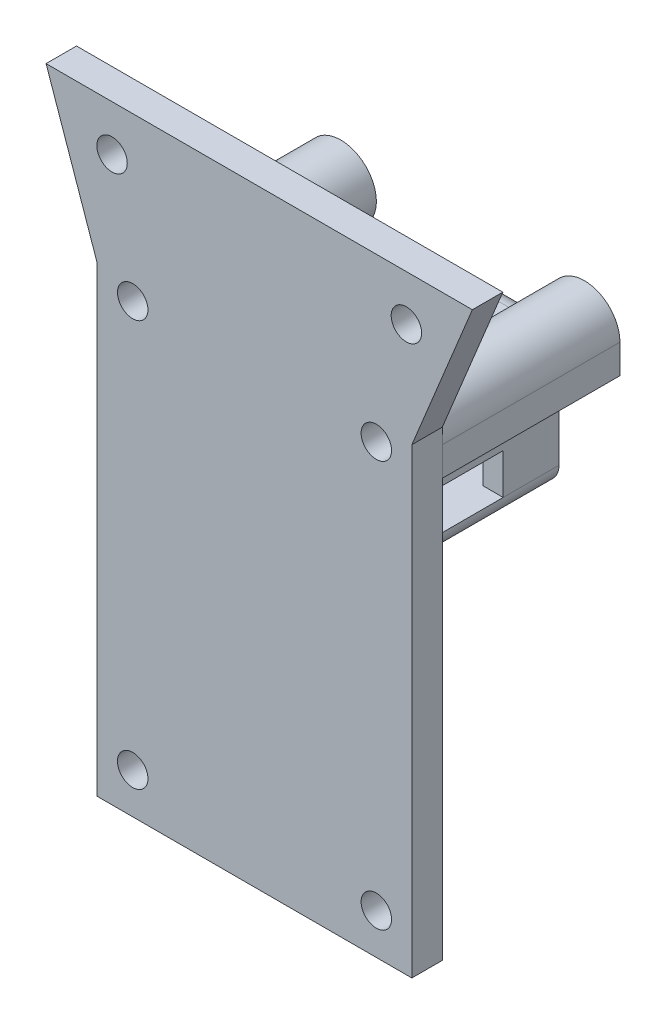
SolidWorks part; units mm, degrees
other "Markup1"
sketch "Sketch10" plane through (36.963, 0, 3) normal (0.1421, -0.5407, 0.8291) x (-0.9838, -0.1695, 0.058)
sketch "Sketch14" plane through (36.963, 0, 3) normal (0.1421, -0.5407, 0.8291) x (-0.9838, -0.1695, 0.058)
ref_plane "Front Plane" through (0, 0, 0) normal (0, 0, 1) x (1, 0, 0)
ref_plane "Top Plane" through (0, 0, 0) normal (0, 1, 0) x (1, 0, 0)
ref_plane "Right Plane" through (0, 0, 0) normal (1, 0, 0) x (0, 0, -1)
sketch "Sketch1" plane through (0, 0, 0) normal (0, 0, 1) x (1, 0, 0)
  line L1 (0, 0) -> (31, 0)
  line L2 (0, 0) -> (0, 45.5)
  line L3 (-5.037, 60) -> (36.963, 60)
  line L4 (31, 0) -> (31, 45.5)
  line L5 (36.963, 60) -> (31, 45.5)
  line L7 (-5.037, 60) -> (0, 45.5)
  circle A0 centre (30.463, 55.5) radius 1.5
  circle A1 centre (27.5, 44) radius 1.5
  circle A4 centre (27.5, 4) radius 1.5
  circle A5 centre (3.5, 4) radius 1.5
  circle A7 centre (3.5, 44) radius 1.5
  circle A9 centre (1.463, 55.5) radius 1.5
  point P29 (15.963, 60)
  dimension "D4" = 3
  dimension "D5" = 21
  dimension "D6" = 2
  dimension "D7" = 2
  dimension "D8" = 21
  dimension "D9" = 2.5
  dimension "D10" = 37
  dimension "D11" = 2.8
  dimension "D12" = 29
  dimension "D13" = 14.5
  dimension "D14" = 11.5
  dimension "D15" = 3
  dimension "D16" = 5
  dimension "D2" = 0
  dimension "D3" = 31
extrude "Boss-Extrude1" add sketch "Sketch1" along normal blind 3
sketch "Sketch2" plane through (0, 0, 0) normal (0, 0, -1) x (-1, 0, 0)
  line L1 (0, 44) -> (0, 24.5)
  line L3 (0, 45.5) -> (0, 0) construction
  line L4 (0, 24.5) -> (-18, 24.5)
  line L8 (-31, 44) -> (-31, 41.136)
  line L9 (-31, 0) -> (-31, 45.5) construction
  line L11 (-18, 24.5) -> (-18, 28.5)
  line L12 (-18, 28.5) -> (-25, 28.5)
  line L14 (-24.0359, 43.5) -> (-6.9641, 43.5)
  line L16 (-25, 28.5) -> (-25, 35.136)
  line L17 (-25, 35.136) -> (-31, 41.136)
  circle A0 centre (-3.5, 44) radius 1.5 construction
  circle A1 centre (-27.5, 44) radius 1.5 construction
  circle A2 centre (-3.5, 44) radius 1.5 construction
  circle A3 centre (-27.5, 44) radius 1.5 construction
  circle A4 centre (-27.5, 44) radius 2.5
  circle A5 centre (-3.5, 44) radius 2.5
  arc A6 (0, 44) -> (-6.9641, 43.5) centre (-3.5, 44) ccw
  arc A7 (-24.0359, 43.5) -> (-31, 44) centre (-27.5, 44) ccw
  dimension "D1" = 5
  dimension "D2" = 7
  dimension "D3" = 5
  dimension "D4" = 7
  dimension "D6" = 18
  dimension "D9" = 2
  dimension "D10" = 45
  dimension "D11" = 2
  dimension "D8" = 15
  dimension "D5" = 19
  dimension "D7" = 25
extrude "Boss-Extrude2" add sketch "Sketch2" along normal blind 1.5 separate body
sketch "Sketch5" plane through (0, 0, -1.5) normal (0, 0, -1) x (-1, 0, 0)
  line L0 (-23, 41.5) -> (-5.5, 41.5)
  line L1 (-5.5, 42.5) -> (-5.5, 41.5)
  line L2 (-6.9641, 43.5) -> (-24.0359, 43.5) construction
  line L3 (-2, 42) -> (-2, 26.5)
  line L4 (-2, 26.5) -> (-16, 26.5)
  line L5 (-16, 26.5) -> (-16, 30.5)
  line L6 (-16, 30.5) -> (-23, 30.5)
  line L7 (-23, 30.5) -> (-23, 41.5)
  line L11 (-6.9641, 43.5) -> (-24.0359, 43.5)
  line L12 (-31, 44) -> (-31, 41.136)
  line L13 (-31, 41.136) -> (-25, 35.136)
  line L14 (-25, 35.136) -> (-25, 28.5)
  line L15 (-25, 28.5) -> (-18, 28.5)
  line L16 (-18, 28.5) -> (-18, 24.5)
  line L17 (-18, 24.5) -> (0, 24.5)
  line L18 (0, 24.5) -> (0, 44)
  line L19 (-6.9641, 43.5) -> (-24.0359, 43.5)
  line L20 (-31, 44) -> (-31, 41.136)
  line L21 (-31, 41.136) -> (-25, 35.136)
  line L22 (-25, 35.136) -> (-25, 28.5)
  line L23 (-25, 28.5) -> (-18, 28.5)
  line L24 (-18, 28.5) -> (-18, 24.5)
  line L25 (-18, 24.5) -> (0, 24.5)
  line L26 (0, 24.5) -> (0, 44)
  circle A0 centre (-3.5, 44) radius 2.5 construction
  circle A1 centre (-27.5, 44) radius 2.5 construction
  arc A2 (-2, 42) -> (-5.5, 42.5) centre (-3.5, 44) ccw
  arc A3 (0, 44) -> (-6.9641, 43.5) centre (-3.5, 44) ccw
  arc A4 (-24.0359, 43.5) -> (-31, 44) centre (-27.5, 44) ccw
  arc A5 (0, 44) -> (-6.9641, 43.5) centre (-3.5, 44) ccw
  arc A6 (-24.0359, 43.5) -> (-31, 44) centre (-27.5, 44) ccw
  circle A7 centre (-27.5, 44) radius 2.5
  dimension "D1" = 2
  dimension "D3" = 2
  dimension "D4" = 2
  dimension "D5" = 2
  dimension "D6" = 2
  dimension "D7" = 2
  dimension "D8" = 2
  dimension "D2" = 0
extrude "Boss-Extrude5" add sketch "Sketch5" along normal blind 14
sketch "Sketch6" plane through (0, 0, -15.5) normal (0, 0, -1) x (-1, 0, 0)
  line L8 (-6.9641, 43.5) -> (-24.0359, 43.5)
  line L9 (-31, 44) -> (-31, 41.136)
  line L10 (-31, 41.136) -> (-25, 35.136)
  line L11 (-25, 35.136) -> (-25, 28.5)
  line L12 (-25, 28.5) -> (-18, 28.5)
  line L13 (-18, 28.5) -> (-18, 24.5)
  line L14 (-18, 24.5) -> (0, 24.5)
  line L15 (0, 24.5) -> (0, 44)
  line L16 (-6.9641, 43.5) -> (-24.0359, 43.5)
  line L17 (-31, 44) -> (-31, 41.136)
  line L18 (-31, 41.136) -> (-25, 35.136)
  line L19 (-25, 35.136) -> (-25, 28.5)
  line L20 (-25, 28.5) -> (-18, 28.5)
  line L21 (-18, 28.5) -> (-18, 24.5)
  line L22 (-18, 24.5) -> (0, 24.5)
  line L23 (0, 24.5) -> (0, 44)
  arc A1 (-2, 42) -> (-5.5, 42.5) centre (-3.5, 44) ccw construction
  arc A2 (0, 44) -> (-6.9641, 43.5) centre (-3.5, 44) ccw
  arc A3 (-24.0359, 43.5) -> (-31, 44) centre (-27.5, 44) ccw
  arc A4 (0, 44) -> (-6.9641, 43.5) centre (-3.5, 44) ccw
  arc A5 (-24.0359, 43.5) -> (-31, 44) centre (-27.5, 44) ccw
  circle A6 centre (-27.5, 44) radius 2.5 construction
  circle A8 centre (-3.5, 44) radius 2.5
  circle A9 centre (-27.5, 44) radius 2.5
  dimension "D1" = 0
extrude "Boss-Extrude6" add sketch "Sketch6" along normal blind 2
sketch "Sketch8" plane through (0, 0, 0) normal (-1, 0, 0) x (0, 0, 1)
  line L0 (-4, 24.5) -> (-4, 33.5)
  line L1 (-17.5, 24.5) -> (0, 24.5) construction
  line L2 (-4, 33.5) -> (-13.5, 33.5)
  line L3 (-13.5, 33.5) -> (-13.5, 24.5)
  line L4 (-13.5, 24.5) -> (-4, 24.5)
  line L5 (0, 24.5) -> (0, 44) construction
  line L6 (-17.5, 24.5) -> (-17.5, 44) construction
  dimension "D1" = 4
  dimension "D2" = 4
  dimension "D3" = 9
extrude "Cut-Extrude1" cut sketch "Sketch8" against normal blind 3
sketch "Sketch9" plane through (0, 24.5, 0) normal (0, -1, 0) x (1, 0, 0)
  line L0 (10, 0) -> (10, -8)
  line L1 (23.1, 0) -> (-23.1, 0) construction
  line L2 (10, -8) -> (22, -8)
  line L3 (22, -8) -> (22, 0)
  line L4 (22, 0) -> (10, 0)
  line L5 (0, -4) -> (0, 0) construction
  dimension "D1" = 10
  dimension "D2" = 8
  dimension "D3" = 12
extrude "Cut-Extrude2" cut sketch "Sketch9" against normal blind 6 contours L0 L2 L3 L4
sketch "Sketch11" plane through (25, 0, 0) normal (1, 0, 0) x (0, 0, -1)
  line L0 (4, 30.5) -> (4, 34.5)
  line L2 (4, 34.5) -> (12, 34.5)
  line L3 (12, 34.5) -> (12, 30.5)
  line L4 (12, 30.5) -> (4, 30.5)
  line L5 (0, 35.136) -> (0, 28.5) construction
  line L6 (17.5, 28.5) -> (0, 28.5) construction
  dimension "D1" = 4
  dimension "D2" = 4
  dimension "D3" = 8
  dimension "D4" = 2
extrude "Cut-Extrude4" cut sketch "Sketch11" against normal blind 2 contours L2 L3 L4 L0
sketch "Sketch12" plane through (0, 0, 0) normal (-1, 0, 0) x (0, 0, 1)
  line L0 (-8.75, 53.5142) -> (-8.75, 17.1339)
  line L1 (-8.75, 17.1339) -> (-21.1273, 17.1339)
  line L2 (-21.1273, 17.1339) -> (-21.1273, 53.5142)
  line L3 (-21.1273, 53.5142) -> (-8.75, 53.5142)
  line L4 (-17.5, 44) -> (0, 44) construction
  point P6 (-8.75, 44)
sketch "Sketch13" plane through (0, 0, 0) normal (0, 0, 1) x (1, 0, 0)
  line L0 (13, 43.5) -> (13, 30.5)
  line L1 (6.9641, 43.5) -> (24.0359, 43.5) construction
  line L2 (22, 30.5) -> (10, 30.5) construction
  line L3 (13, 30.5) -> (18, 30.5)
  line L4 (18, 30.5) -> (18, 43.5)
  line L5 (18, 43.5) -> (13, 43.5)
  line L6 (6.9641, 43.5) -> (24.0359, 43.5) construction
  point P6 (15.5, 43.5)
  point P9 (15.5, 43.5)
  dimension "D1" = 5
extrude "Cut-Extrude7" cut sketch "Sketch13" against normal up to surface (1.5 mm away) up to face at (11.456, 34.5861, -1.5)
sketch "Sketch15" plane through (0, 43.5, 0) normal (0, 1, 0) x (1, 0, 0)
  line L0 (9.5, 0) -> (9.5, 13.5)
  line L1 (9.5, 13.5) -> (21.5, 13.5)
  line L2 (21.5, 13.5) -> (21.5, 0)
  line L3 (21.5, 0) -> (9.5, 0)
  line L4 (6.9641, 0) -> (13, 0) construction
  line L5 (6.9641, 17.5) -> (24.0359, 17.5) construction
  point P8 (15.5, 17.5)
  point P9 (15.5, 13.5)
  dimension "D1" = 12
  dimension "D2" = 4
extrude "Cut-Extrude8" cut sketch "Sketch15" against normal blind 2
fillet "Fillet1" radius 2 13 edges at (18, 41.5, -0.75) (13, 41.5, -0.75) (13, 30.5, -0.75) (18, 30.5, -0.75) (14.25, 41.5, -15.5) (15.5, 43.5, -17.5) (25, 28.5, -8.75) (18, 24.5, -12.75) (16, 30.5, -11.75) (18, 28.5, -12.75) (0, 24.5, -15.5) (0, 24.5, -2) (2, 26.5, -2.75)
sketch "Sketch16" plane through (-5.068, 5.068, 0) normal (0.7071, -0.7071, 0) x (0, 0, -1)
  line L0 (13.5, 45.6084) -> (1.5, 45.6084) construction
  line L1 (13.5, 45.6084) -> (1.5, 45.6084) construction
  line L2 (0, 53.0581) -> (0, 48.0581) construction
  line L3 (0, 53.0581) -> (0, 48.0581) construction
  line L4 (0, 51.0079) -> (0, 42.5226)
  line L5 (0, 42.5226) -> (17.5, 42.5226)
  line L6 (17.5, 42.5226) -> (17.5, 51.0079)
  line L7 (17.5, 51.0079) -> (0, 51.0079)
  line L8 (0, 51.0079) -> (0, 48.0581) construction
  line L12 (13.5, 45.6084) -> (1.5, 45.6084) construction
  line L13 (0, 48.0581) -> (17.5, 48.0581) construction
  line L14 (3, 50.6084) -> (3, 46.6084)
  line L16 (13, 46.6084) -> (13, 50.6084)
  line L17 (13, 50.6084) -> (3, 50.6084)
  line L20 (4, 40.6586) -> (4, 42.0729) construction
  line L21 (12, 40.6586) -> (12, 42.0729) construction
  line L22 (3, 46.6084) -> (13, 46.6084)
  dimension "D2" = 10
  dimension "D3" = 1
  dimension "D4" = 1
  dimension "D5" = 4
  dimension "D6" = 1
  dimension "D1" = 0
extrude "Cut-Extrude9" cut sketch "Sketch16" against normal through all contours L14 L22 L16 L17
